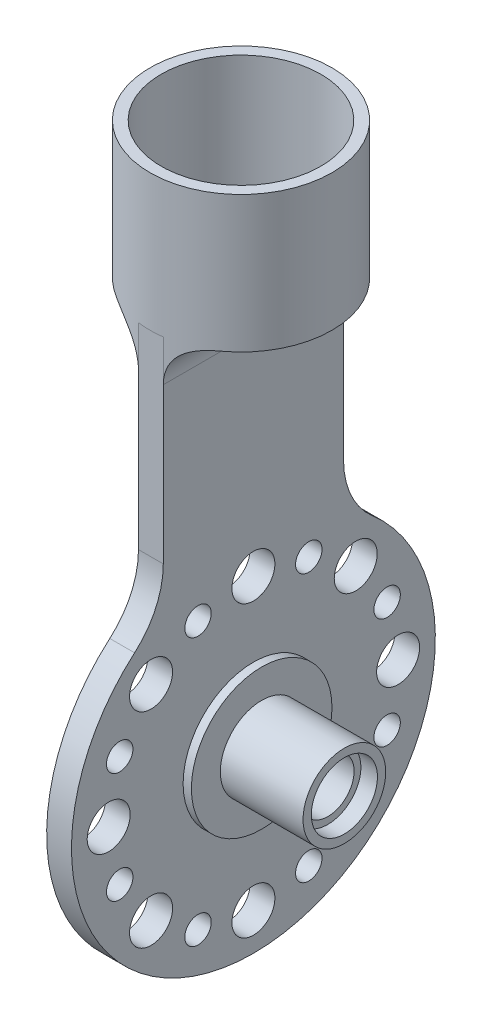
SolidWorks part; units mm, degrees
material "7075-T6 (SN)"
ref_plane "Front Plane" through (0, 0, 0) normal (0, 0, 1) x (1, 0, 0)
ref_plane "Top Plane" through (0, 0, 0) normal (0, 1, 0) x (1, 0, 0)
ref_plane "Right Plane" through (0, 0, 0) normal (1, 0, 0) x (0, 0, -1)
sketch "Sketch2" plane through (0, 0, 0) normal (0, 1, 0) x (-1, 0, 0)
  circle A0 centre (0, 0) radius 11
  dimension "D1" = 22
extrude "Boss-Extrude2" add sketch "Sketch2" against normal blind 1.5
sketch "Sketch3" plane through (0, 0, 0) normal (0, -1, 0) x (-1, 0, 0)
  circle A0 centre (0, 0) radius 9.652
  circle A1 centre (0, 0) radius 11
  circle A3 centre (0, 0) radius 11 construction
  dimension "D2" = 19.304
extrude "Boss-Extrude3" add sketch "Sketch3" against normal blind 15
sketch "Sketch4" plane through (0, -1.5, 0) normal (0, -1, 0) x (1, 0, 0)
  line L1 (-1.5, 10.8972) -> (1.5, 10.8972)
  line L2 (-1.5, 10.8972) -> (-1.5, -10.8972)
  line L3 (-1.5, -10.8972) -> (1.5, -10.8972)
  line L4 (1.5, 10.8972) -> (1.5, -10.8972)
  line L5 (-1.5, 10.8972) -> (1.5, -10.8972) construction
  line L6 (-1.5, -10.8972) -> (1.5, 10.8972) construction
  circle A0 centre (0, 0) radius 11 construction
  arc A1 (1.5, 10.8972) -> (-1.5, 10.8972) centre (0, 0) ccw construction
  arc A2 (-1.5, -10.8972) -> (1.5, -10.8972) centre (0, 0) ccw construction
  point P0 (0, 0)
  dimension "D1" = 3
extrude "Boss-Extrude4" add sketch "Sketch4" along normal blind 58
sketch "Sketch7" plane through (1.5, 0, 0) normal (1, 0, 0) x (0, 0, -1)
  line L0 (10.8972, -59.5) -> (-10.8972, -59.5) construction
  line L1 (0, -49.5) -> (0, -59.5) construction
  circle A0 centre (0, -49.5) radius 11.5 construction
  circle A2 centre (0, -38) radius 2.1
  circle A3 centre (11.5, -49.5) radius 2.1
  circle A4 centre (0, -61) radius 2.1
  circle A5 centre (-11.5, -49.5) radius 2.1
  dimension "D1" = 23
  dimension "D2" = 4.2
  dimension "D3" = 10
extrude "Cut-Extrude2" [suppressed] cut sketch "Sketch7" against normal up to surface (3 mm away)
ref_plane "Plane1" through (0, 0, 0) normal (-1, 0, 0) x (0, 0, 1)
sketch "Sketch11" plane through (1.5, 0, 0) normal (1, 0, 0) x (0, 0, -1)
  line L0 (10.8972, -59.5) -> (-10.8972, -59.5) construction
  circle A0 centre (0, -49.5) radius 8.5
  dimension "D1" = 17
  dimension "D2" = 10
extrude "Boss-Extrude11" add sketch "Sketch11" along normal blind 1 contours A0
sketch "Sketch8" plane through (2.5, 0, 0) normal (-1, 0, 0) x (0, 0, 1)
  circle A0 centre (0, -49.5) radius 5
  circle A1 centre (0, -49.5) radius 8.5 construction
  dimension "D1" = 10
extrude "Boss-Extrude6" add sketch "Sketch8" against normal blind 10 contours A0
sketch "Sketch17" plane through (-1.5, 0, 0) normal (-1, 0, 0) x (0, 0, 1)
  circle A1 centre (0, -49.5) radius 8.5
  circle A2 centre (0, -49.5) radius 5 construction
  dimension "D1" = 17
sketch "Sketch15" plane through (12.5, 0, 0) normal (1, 0, 0) x (0, 0, -1)
  circle A0 centre (0, -49.5) radius 3.175
  dimension "D1" = 6.35
extrude "encoder_bed" cut sketch "Sketch15" against normal blind 6
fillet "Fillet5" radius 10 2 edges at (0, -59.5, -10.8972) (0, -59.5, 10.8972)
ref_plane "Plane2" through (0, 0, 0) normal (-1, 0, 0) x (0, 0, 1)
ref_axis "Axis1" through (20.3679, -49.5, 0) along (-1, 0, 0)
sketch "Sketch20" plane through (0, 0, 0) normal (0, 0, 1) x (1, 0, 0)
  line L0 (-10.5, -1.5) -> (-1.5, -1.5)
  line L1 (-1.5, -1.5) -> (-1.5, -15.5)
  line L2 (-1.5, -49.5) -> (-1.5, -1.5) construction
  line L3 (-1.5, -15.5) -> (-10.5, -1.5)
  line L4 (-1.5, -15.5) -> (1.5, -15.5) construction
  line L5 (1.5, -49.5) -> (1.5, -1.5) construction
  line L6 (1.5, -15.5) -> (10.5, -1.5)
  line L7 (10.5, -1.5) -> (1.5, -1.5)
  line L8 (1.5, -1.5) -> (1.5, -15.5)
  dimension "D1" = 14
  dimension "D2" = 9
extrude "Boss-Extrude12" [suppressed] add sketch "Sketch20" along normal mid plane 3
fillet "Fillet6" [suppressed] radius 2
fillet "Fillet7" radius 5 2 edges at (-1.5, -1.5, 0) (1.5, -1.5, 0)
sketch "Sketch21" plane through (12.5, 0, 0) normal (1, 0, 0) x (0, 0, -1)
  circle A0 centre (0, -49.5) radius 4
  dimension "D1" = 8
extrude "Cut-Extrude6" cut sketch "Sketch21" against normal blind 2
sketch "Sketch22" plane through (-1.5, 0, 0) normal (-1, 0, 0) x (0, 0, 1)
  circle A0 centre (0, -49.5) radius 22
  dimension "D1" = 44
extrude "Boss-Extrude13" add sketch "Sketch22" against normal up to surface (3 mm away) up to face at (1.5, -49.5, 8.5)
sketch "Sketch23" plane through (-1.5, 0, 0) normal (-1, 0, 0) x (0, 0, 1)
  circle A0 centre (0, -49.5) radius 17.5 construction
  circle A1 centre (0, -32) radius 2.6
  dimension "D1" = 35
  dimension "D2" = 5.2
extrude "Cut-Extrude7" cut sketch "Sketch23" against normal up to surface (3 mm away) up to face at (1.5, -28.7221, 0)
pattern_circular "CirPattern1" count 8 over 360 about axis through (63.7254, -49.5, 0) along (-1, 0, 0) of "Cut-Extrude7"
sketch "Sketch24" plane through (-1.5, 0, 0) normal (-1, 0, 0) x (0, 0, 1)
  line L0 (0, -49.5) -> (6.697, -33.3321) construction
  line L1 (0, -49.5) -> (0, -32) construction
  line L3 (12.3744, -37.1256) -> (0, -49.5) construction
  line L4 (0, -32) -> (6.697, -33.3321) construction
  line L5 (6.697, -33.3321) -> (12.3744, -37.1256) construction
  circle A0 centre (0, -49.5) radius 17.5
  circle A1 centre (6.697, -33.3321) radius 1.6
  dimension "D1" = 35
  dimension "D2" = 3.2
extrude "Cut-Extrude8" cut sketch "Sketch24" against normal up to surface (3 mm away) contours A1 up to face at (1.5, -37.1256, 14.9744)
pattern_circular "CirPattern2" count 8 over 360 about axis through (63.7254, -49.5, 0) along (-1, 0, 0) of "Cut-Extrude8"
fillet "Fillet8" radius 10 2 edges at (0, -30.3885, -10.8972) (0, -30.3885, 10.8972)
